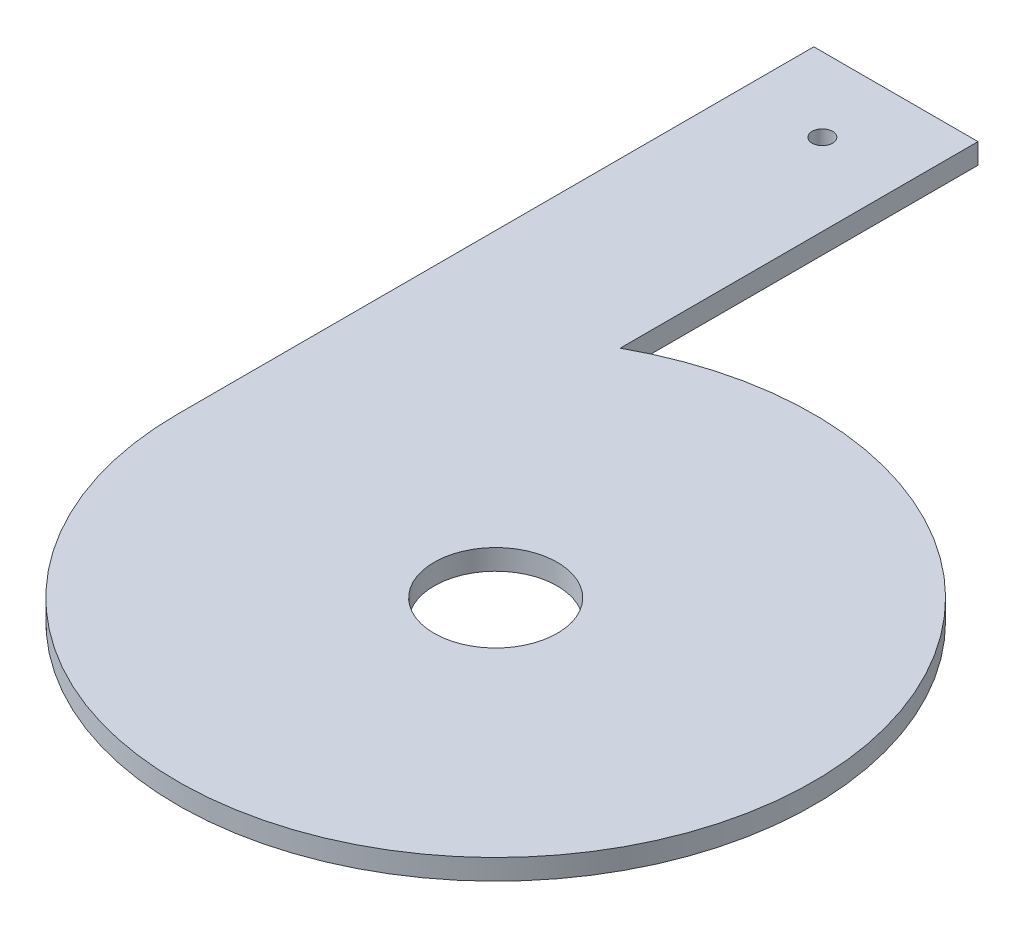
SolidWorks part; units mm, degrees
ref_plane "Front Plane" through (0, 0, 0) normal (0, 0, 1) x (1, 0, 0)
ref_plane "Top Plane" through (0, 0, 0) normal (0, 1, 0) x (1, 0, 0)
ref_plane "Right Plane" through (0, 0, 0) normal (1, 0, 0) x (0, 0, -1)
sketch "Sketch1" plane through (0, 0, 0) normal (0, 1, 0) x (1, 0, 0)
  circle A0 centre (0, 0) radius 31
extrude "Boss-Extrude1" add sketch "Sketch1" along normal blind 2
sketch "Sketch2" plane through (0, 2, 0) normal (0, 1, 0) x (1, 0, 0)
  circle A0 centre (0, 0) radius 6
extrude "Cut-Extrude1" cut sketch "Sketch2" against normal blind 2
sketch "Sketch3" plane through (0, 2, 0) normal (0, 1, 0) x (1, 0, 0)
  line L1 (-31, 0) -> (-15, 0)
  line L2 (-31, 0) -> (-31, 62)
  line L3 (-31, 62) -> (-15, 62)
  line L4 (-15, 0) -> (-15, 62)
  circle A0 centre (0, 0) radius 31 construction
  dimension "D1" = 62
  dimension "D2" = 16
extrude "Boss-Extrude2" add sketch "Sketch3" against normal blind 2
sketch "Sketch4" plane through (0, 2, 0) normal (0, 1, 0) x (1, 0, 0)
  line L3 (-15, 27.1293) -> (-15, 62)
  line L4 (-15, 62) -> (-31, 62)
  line L5 (-31, 62) -> (-31, 0)
  line L6 (-15, 27.1293) -> (-15, 62)
  line L7 (-15, 62) -> (-31, 62)
  line L8 (-31, 62) -> (-31, 0)
  line L10 (-20, 48.33) -> (-20, 61.23)
  line L11 (-25.9, 48.33) -> (-20, 48.33)
  line L12 (-25.9, 61.23) -> (-25.9, 48.33)
  line L13 (-20, 61.23) -> (-25.9, 61.23)
  line L14 (-20, 48.33) -> (-20, 61.23)
  line L15 (-25.9, 48.33) -> (-20, 48.33)
  line L16 (-25.9, 61.23) -> (-25.9, 48.33)
  line L17 (-20, 61.23) -> (-25.9, 61.23)
  arc A1 (-31, 0) -> (-15, 27.1293) centre (0, 0) ccw
  arc A2 (-31, 0) -> (-15, 27.1293) centre (0, 0) ccw
  dimension "D1" = 0
  dimension "D2" = 0
sketch "Sketch8" plane through (0, 0, 0) normal (0, -1, 0) x (1, 0, 0)
  circle A0 centre (-22.95, -54.78) radius 1 construction
  circle A1 centre (-22.95, -54.78) radius 1
sketch "Sketch10" plane through (0, 2, 0) normal (0, 1, 0) x (1, 0, 0)
  line L4 (-20, 48.33) -> (-20, 61.23)
  line L5 (-25.9, 48.33) -> (-20, 48.33)
  line L6 (-25.9, 61.23) -> (-25.9, 48.33)
  line L7 (-20, 61.23) -> (-25.9, 61.23)
  line L8 (-20, 48.33) -> (-20, 61.23)
  line L9 (-25.9, 48.33) -> (-20, 48.33)
  line L10 (-25.9, 61.23) -> (-25.9, 48.33)
  line L11 (-20, 61.23) -> (-25.9, 61.23)
  dimension "D1" = 0
sketch "Sketch11" plane through (0, 2, 0) normal (0, 1, 0) x (1, 0, 0)
  line L3 (-20, 61.23) -> (-25.9, 61.23) construction
  circle A0 centre (-22.95, 54.78) radius 1
  point P6 (-35.7895, 57.7855)
  dimension "D1" = 6.45
extrude "Cut-Extrude2" cut sketch "Sketch11" against normal up to next
